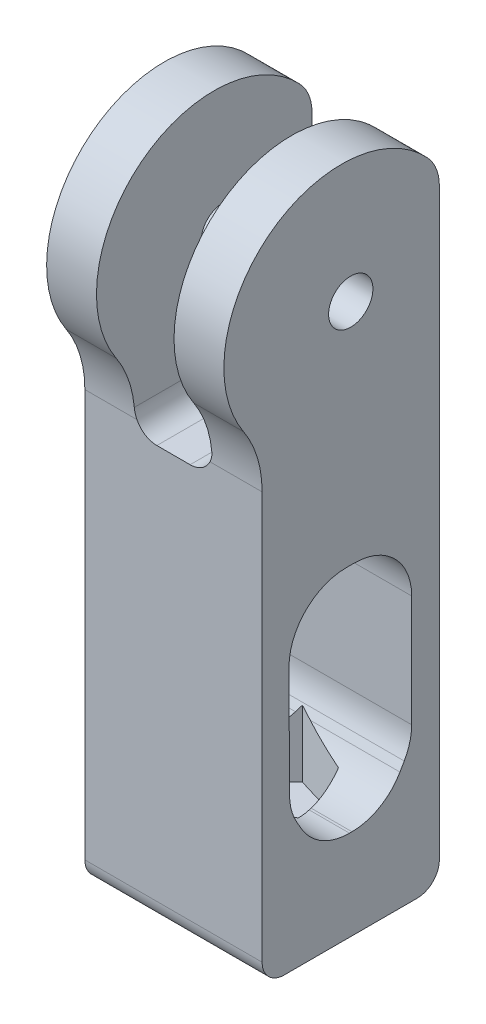
SolidWorks part; units mm, degrees
material "ABS generico"
ref_plane "Piano frontale" through (0, 0, 0) normal (0, 0, 1) x (1, 0, 0)
ref_plane "Piano superiore" through (0, 0, 0) normal (0, 1, 0) x (1, 0, 0)
ref_plane "Piano destro" through (0, 0, 0) normal (1, 0, 0) x (0, 0, -1)
sketch "Sketch9" plane through (0, 0, 0) normal (1, 0, 0) x (0, 0, -1)
  line L0 (8, 5.0539) -> (8, -49.642)
  line L1 (8, -49.642) -> (-8, -49.642)
  line L2 (-8, -49.642) -> (-8, -10.8758)
  line L3 (5.5, -41.5) -> (5.5, -25.7624)
  line L5 (0.3362, -20.5986) -> (-0.4104, -20.5986)
  line L6 (-5.5741, -25.7867) -> (-5.5, -41.5)
  line L7 (-5.5, -41.5) -> (5.5, -41.5)
  line L8 (0, -49.642) -> (0, 21.1385) construction
  circle A0 centre (0, 0) radius 2
  arc A1 (6.9253, 7.782) -> (-9.6743, -5.3367) centre (-0.8371, 0.5427) ccw
  arc A2 (-8, -10.8758) -> (-9.6743, -5.3367) centre (-18, -10.8758) ccw
  arc A3 (8, 5.0539) -> (6.9253, 7.782) centre (4, 5.0539) ccw
  arc A4 (5.5, -25.7624) -> (0.3362, -20.5986) centre (0.3362, -25.7624) ccw
  arc A5 (-5.5741, -25.7867) -> (-0.4104, -20.5986) centre (-0.4104, -25.7624) cw
  point P24 (8, 6.4221)
  dimension "D1" = 4
  dimension "D2" = 10
  dimension "D3" = 4
  dimension "D4" = 5.1638
  dimension "D5" = 16
extrude "Boss-Extrude3" add sketch "Sketch9" along normal blind 16
sketch "Sketch10" plane through (0, -49.642, 0) normal (0, -1, 0) x (1, 0, 0)
  line L0 (8, 8) -> (8, -8) construction
  line L1 (16, 8) -> (0, 8) construction
  line L2 (16, -8) -> (0, -8) construction
  line L3 (0, 0) -> (18.4029, 0) construction
  line L5 (0, 8) -> (0, -8) construction
  circle A0 centre (8, 0) radius 2
  point P11 (8, 0)
  dimension "D1" = 4
extrude "Cut-Extrude7" cut sketch "Sketch10" against normal blind 14
ref_plane "Plane1" through (0, 16, 0) normal (0, 1, 0) x (1, 0, 0)
sketch "Sketch11" plane through (0, 16, 0) normal (0, 1, 0) x (1, 0, 0)
  line L0 (8, 8) -> (8, -11.4514) construction
  line L1 (16, 8) -> (0, 8) construction
  line L2 (0, -11.4514) -> (16, -11.4514) construction
  line L4 (11.5, -16.0809) -> (4.5, -16.0809)
  line L5 (11.5, -16.0809) -> (11.5, 10.6052)
  line L6 (11.5, 10.6052) -> (4.5, 10.6052)
  line L7 (4.5, -16.0809) -> (4.5, 10.6052)
  line L8 (11.5, -16.0809) -> (4.5, 10.6052) construction
  line L9 (11.5, 10.6052) -> (4.5, -16.0809) construction
  point P6 (8, -2.7378)
  dimension "D1" = 7
extrude "Cut-Extrude8" cut sketch "Sketch11" against normal blind 28
fillet "Fillet1" radius 2 2 edges at (8, -49.642, -8) (8, -49.642, 8)
chamfer "Chamfer1" distance 2.5 angle 60 2 edges at (8, -41.5, 5.5) (8, -41.5, -5.5) first distance on face at (8, -41.5, 2)
sketch "Sketch12" plane through (0, -41.5, 0) normal (0, 1, 0) x (1, 0, 0)
  line L1 (6.8952, 4.7506) -> (3.3335, 1.4185)
  line L2 (3.3335, 1.4185) -> (4.4383, -3.3321)
  line L3 (4.4383, -3.3321) -> (9.1048, -4.7506)
  line L4 (9.1048, -4.7506) -> (12.6665, -1.4185)
  line L5 (12.6665, -1.4185) -> (11.5617, 3.3321)
  line L6 (11.5617, 3.3321) -> (6.8952, 4.7506)
  circle A0 centre (8, 0) radius 4.8774 construction
extrude "Extrude1" cut sketch "Sketch12" against normal blind 3 and the other way blind 3
fillet "Fillet2" radius 2 2 edges at (4.5, -12, 0) (11.5, -12, 0)
fillet "Fillet3" radius 5 2 edges at (8, -37.1699, -5.5) (8, -37.1342, 5.5206)
fillet "Fillet4" radius 5 4 edges at (2.512, -41.5, -3) (13.8195, -41.5, -3) (2.1805, -41.5, 3) (13.488, -41.5, 3)
